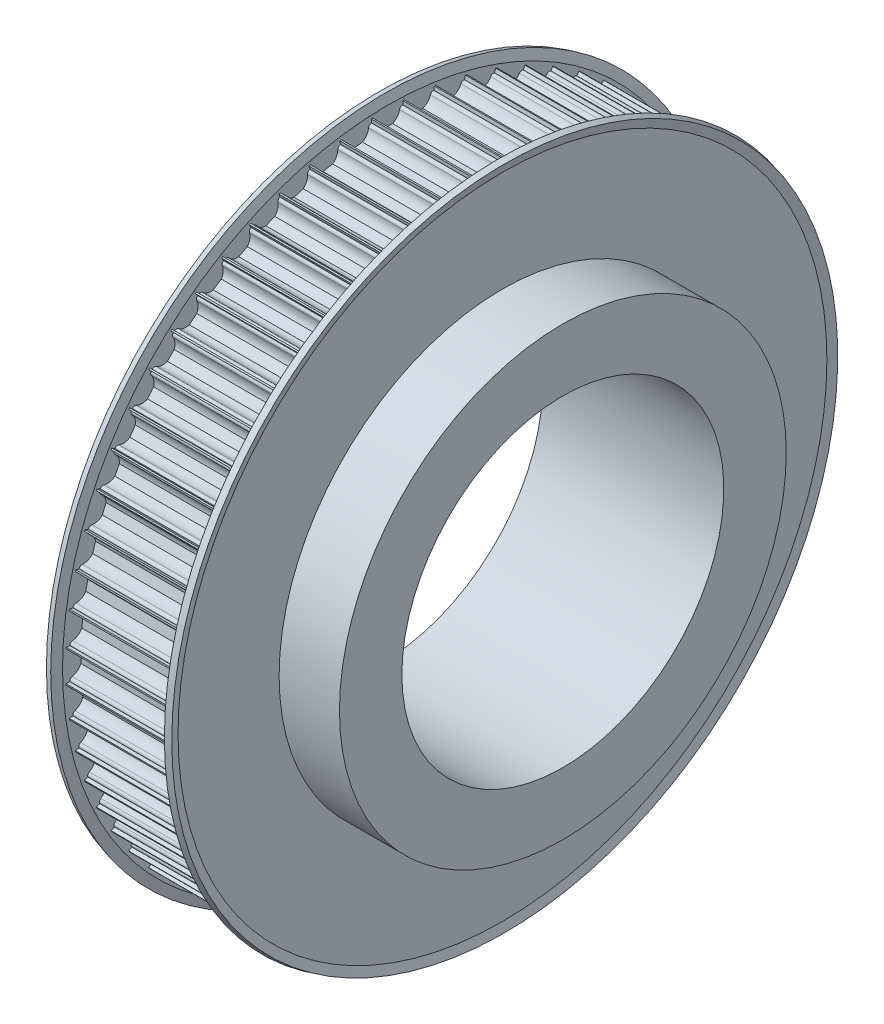
SolidWorks part; units mm, degrees
ref_plane "Front Plane" through (0, 0, 0) normal (0, 0, 1) x (1, 0, 0)
ref_plane "Top Plane" through (0, 0, 0) normal (0, 1, 0) x (1, 0, 0)
ref_plane "Right Plane" through (0, 0, 0) normal (1, 0, 0) x (0, 0, -1)
sketch "Sketch1" plane through (0, 0, 0) normal (0, 0, 1) x (1, 0, 0)
  line L0 (0, 0) -> (68.4122, 0) construction
  line L1 (0, 68.8194) -> (0, 40)
  line L2 (0, 40) -> (45, 40)
  line L3 (45, 40) -> (45, 55.5)
  line L4 (45, 55.5) -> (30, 55.5)
  line L5 (30, 55.5) -> (30, 80)
  line L7 (0, 80) -> (0, 68.8194)
  line L8 (30, 80) -> (0, 80)
  dimension "D1" = 30
  dimension "D2" = 15
  dimension "D3" = 15.5
  dimension "D4" = 80
  dimension "D5" = 40
revolve "Revolve1" add sketch "Sketch1" angle 360 about L0
sketch "Sketch2" plane through (0, 0, 0) normal (-1, 0, 0) x (0, 0, 1)
  line L0 (3.6742, 79) -> (3.75, 79)
  line L1 (3.75, 79) -> (3.75, 81)
  line L2 (3.75, 81) -> (-3.75, 81)
  line L3 (-3.75, 81) -> (-3.75, 79)
  line L4 (-3.75, 79) -> (-3.6742, 79)
  line L5 (-1.199, 76.25) -> (1.199, 76.25)
  arc A0 (-2.9394, 78.4) -> (-1.199, 76.25) centre (0, 79) ccw
  arc A1 (-3.6742, 79) -> (-2.9394, 78.4) centre (-3.6742, 78.25) cw
  arc A2 (2.9394, 78.4) -> (3.6742, 79) centre (3.6742, 78.25) cw
  arc A3 (1.199, 76.25) -> (2.9394, 78.4) centre (0, 79) ccw
  point P11 (0, 81)
  point P14 (-3, 79)
  dimension "D1" = 79
  dimension "D4" = 3
  dimension "D5" = 0.75
  dimension "D6" = 0.75
  dimension "D2" = 2
  dimension "D3" = 7.5
  dimension "D7" = 2.75
extrude "Cut-Extrude1" cut sketch "Sketch2" against normal up to next
pattern_circular "CirPattern1" count 64 over 360 about axis through (0, 0, 0) along (-1, 0, 0) of "Cut-Extrude1"
sketch "Sketch3" plane through (0, 0, 0) normal (0, 0, 1) x (1, 0, 0)
  line L0 (15, 79.8948) -> (15, 50.1986) construction
  line L1 (30, 79.8948) -> (0, 79.8948) construction
  line L2 (30, 55.5) -> (30, 80.61)
  line L3 (30, 80.61) -> (30.5701, 82.7375)
  line L4 (30.5701, 82.7375) -> (29.1212, 83.1257)
  line L5 (28.5, 80.8075) -> (28.5, 55.5)
  line L6 (28.5, 55.5) -> (30, 55.5)
  line L7 (28.5, 80.8075) -> (29.1212, 83.1257)
  line L8 (1.5, 80.8075) -> (1.5, 55.5)
  line L9 (1.5, 55.5) -> (0, 55.5)
  line L10 (0, 55.5) -> (0, 80.61)
  line L11 (0, 80.61) -> (-0.5701, 82.7375)
  line L12 (-0.5701, 82.7375) -> (0.8788, 83.1257)
  line L13 (1.5, 80.8075) -> (0.8788, 83.1257)
  line L14 (0, 0) -> (35.1403, 0) construction
  dimension "D2" = 15
  dimension "D1" = 1.5
  dimension "D3" = 1.5
  dimension "D4" = 25.11
  dimension "D5" = 2.4
revolve "Revolve2" add sketch "Sketch3" angle 360 about L14
